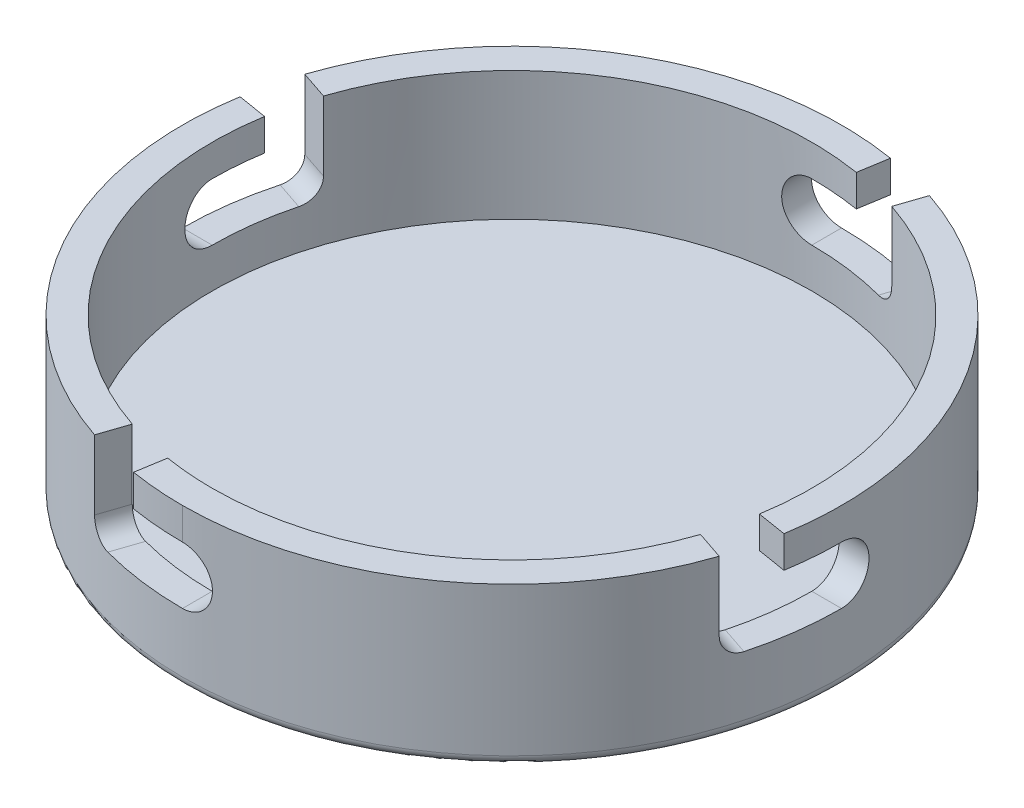
SolidWorks part; units mm, degrees
ref_plane "Front Plane" through (0, 0, 0) normal (0, 0, 1) x (1, 0, 0)
ref_plane "Top Plane" through (0, 0, 0) normal (0, 1, 0) x (1, 0, 0)
ref_plane "Right Plane" through (0, 0, 0) normal (1, 0, 0) x (0, 0, -1)
sketch "Sketch1" plane through (0, 0, 0) normal (0, 1, 0) x (1, 0, 0)
  circle A0 centre (0, 0) radius 15.125
  circle A1 centre (0, 0) radius 16.625
  dimension "D1" = 30.25
  dimension "D2" = 1.5
extrude "Boss-Extrude1" add sketch "Sketch1" along normal blind 6.5
extrude "Boss-Extrude2" add sketch "Sketch1<6>" against normal blind 1.5 contours A0 | A1 A0 region at (0, 0, 0) region at (-16.1548, 0, 0)
sketch "Sketch1<6>" plane through (0, 0, 0) normal (0, 1, 0) x (1, 0, 0) same geometry as "Sketch1"
ref_plane "Plane1" through (15.125, 0, 0) normal (-1, 0, 0) x (0, 0, 1)
sketch "Sketch3" plane through (15.125, 0, 0) normal (-1, 0, 0) x (0, 0, 1)
  line L0 (0, 0) -> (0, 6.5) construction
  line L1 (15.125, 6.5) -> (-15.125, 6.5) construction
  line L3 (0, 4.9) -> (3.55, 4.9)
  line L4 (0, 3.45) -> (5, 3.45) construction
  line L5 (3.55, 4.9) -> (6.45, 2) construction
  line L6 (0, 2) -> (6.45, 2)
  line L7 (3.55, 4.9) -> (3.55, 6.5)
  line L8 (6.45, 2) -> (6.45, 6.5)
  line L9 (6.45, 6.5) -> (3.55, 6.5)
  line L10 (16.625, 6.5) -> (-16.625, 6.5) construction
  circle A0 centre (0, 3.25) radius 1.25 construction
  circle A1 centre (0, 3.45) radius 1.45
  point P18 (1.45, 3.45)
  point P19 (0, 0)
  point P20 (0, 0)
  dimension "D1" = 2.5
  dimension "D4" = 2.9
  dimension "D2" = 3.25
  dimension "D3" = 0.2
  dimension "D5" = 135
  dimension "D6" = 5
extrude "Cut-Extrude1" cut sketch "Sketch3" against normal blind 1.5 and the other way blind 1.5 contours A1
ref_axis "Axis1" through (14.9731, 3.45, 0) along (1, 0, 0)
ref_plane "Plane4" through (0, 3.45, 0) normal (0, 1, 0) x (1, 0, 0)
sketch "Sketch5" plane through (0, 3.45, 0) normal (0, 1, 0) x (1, 0, 0)
  line L0 (16.625, 0) -> (0, 0)
  line L1 (0, 0) -> (16.1348, -4.0075)
  line L3 (14.9731, 0) -> (16.625, 0) construction
  line L4 (15.7566, -5.3027) -> (0, 0)
  line L5 (16.4066, -2.686) -> (0, 0)
  arc A0 (16.625, 0) -> (16.1348, -4.0075) centre (0, 0) cw
  arc A1 (16.5616, -1.45) -> (16.5616, 1.45) centre (0, 0) ccw construction
  circle A2 centre (0, 0) radius 16.625 construction
  arc A3 (16.4066, -2.686) -> (15.7566, -5.3027) centre (0, 0) cw
  point P15 (16.1348, -4.0075)
  dimension "D1" = 9.302
  dimension "D2" = 18.6
ref_plane "Plane5" through (0, 2, 0) normal (0, 1, 0) x (1, 0, 0)
ref_plane "Plane6" through (0, 4.9, 0) normal (0, -1, 0) x (-1, 0, 0)
extrude "Cut-Extrude2" cut sketch "Sketch5" against normal up to surface (1.45 mm away) and the other way up to surface (1.45 mm away) contours A0 L0 L5 | A0 L5 L1 region at (11.0348, 3.45, 0.8973) region at (10.8531, 3.45, 2.2324) up to plane "Plane5" other way up to plane "Plane6"
extrude "Cut-Extrude3" cut sketch "Sketch5<4>" against normal up to surface (1.45 mm away) and the other way through all contours A3 L1 L4 | A0 L5 L1 region at (10.8531, 3.45, 2.2324) region at (10.6363, 3.45, 3.1051) up to plane "Plane5"
sketch "Sketch5<4>" plane through (0, 3.45, 0) normal (0, 1, 0) x (1, 0, 0) same geometry as "Sketch5"
fillet "Fillet1" radius 0.5 1 edges at (0, -1.5, 16.625)
fillet "Fillet2" radius 1 1 edges at (15.0458, 2, 5.0635)
pattern_circular "CirPattern3" count 4 over 360 about axis through (0, -1, 0) along (0, 1, 0) of "Cut-Extrude3", "Cut-Extrude2", "Fillet2", "Cut-Extrude1"
equation "\"D4@Sketch3\"= \"D3@Sketch3\" * 2 + 2.5"
